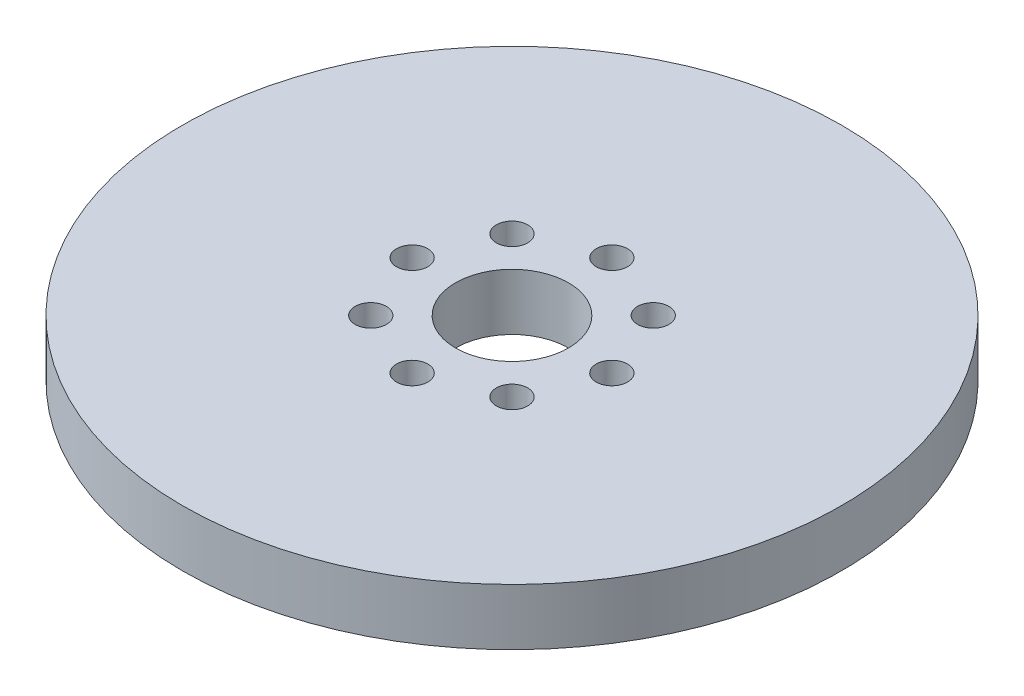
SolidWorks part; units mm, degrees
ref_plane "Front Plane" through (0, 0, 0) normal (0, 0, 1) x (1, 0, 0)
ref_plane "Top Plane" through (0, 0, 0) normal (0, 1, 0) x (1, 0, 0)
ref_plane "Right Plane" through (0, 0, 0) normal (1, 0, 0) x (0, 0, -1)
sketch "Sketch1" plane through (0, 0, 0) normal (0, 1, 0) x (1, 0, 0)
  circle A0 centre (0, 0) radius 87.5
  dimension "FLANGE_OD" = 175
extrude "Boss-Extrude1" add sketch "Sketch1" along normal blind 15
sketch "Sketch2" plane through (0, 0, 0) normal (0, 1, 0) x (1, 0, 0)
  circle A0 centre (0, 0) radius 15
  dimension "BORE_D" = 30
extrude "Cut-Extrude1" cut sketch "Sketch2" along normal through all
sketch "Sketch3" plane through (0, 15, 0) normal (0, 1, 0) x (1, 0, 0)
  circle A0 centre (0, 0) radius 26.5165 construction
  circle A1 centre (-26.5165, 0) radius 4.1618
  dimension "BOLT_D" = 8.3236
  dimension "BOLT_PCD" = 53.033
extrude "Cut-Extrude2" cut sketch "Sketch3" against normal blind 12.7898
pattern_circular "CirPattern1" count 8 over 360 about axis through (0, 0, 0) along (0, 1, 0) of "Cut-Extrude2"
